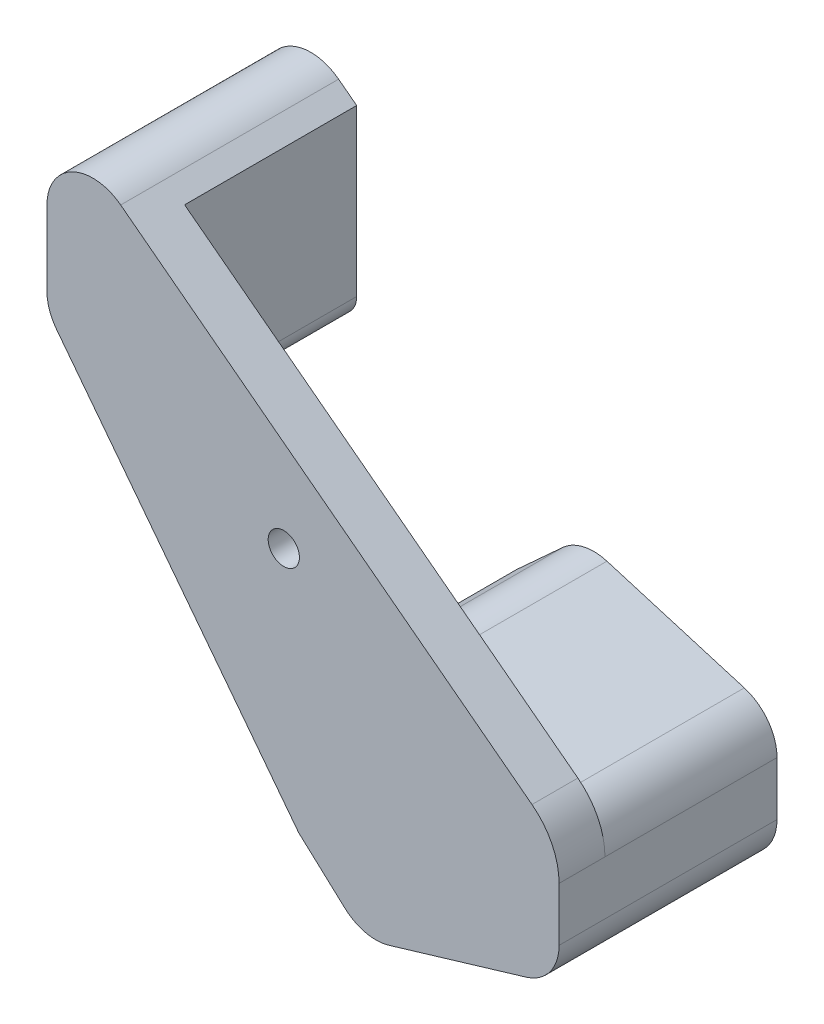
SolidWorks part; units mm, degrees
ref_plane "Front Plane" through (0, 0, 0) normal (0, 0, 1) x (1, 0, 0)
ref_plane "Top Plane" through (0, 0, 0) normal (0, 1, 0) x (1, 0, 0)
ref_plane "Right Plane" through (0, 0, 0) normal (1, 0, 0) x (0, 0, -1)
sketch "Sketch1" plane through (0, 0, 0) normal (0, 0, 1) x (1, 0, 0)
  line L0 (0, 0) -> (0, 12.7)
  line L1 (0, 12.7) -> (11.1125, 22.86)
  line L3 (11.1125, 22.86) -> (38.1, 14.7942)
  line L4 (38.1, 14.7942) -> (38.1, -19.05)
  line L5 (11.1125, 12.7) -> (11.1125, 0) construction
  line L6 (11.1125, 6.35) -> (30.1625, 6.35) construction
  line L7 (11.1125, -10.16) -> (38.1, -2.0942)
  line L8 (0, 0) -> (11.1125, -10.16)
  circle A0 centre (11.1125, 12.7) radius 2.032
  circle A1 centre (11.1125, 0) radius 2.032
  circle A2 centre (30.1625, 6.35) radius 2.032
  dimension "D3" = 4.064
  dimension "D1" = 73.36
  dimension "D2" = 38.1
  dimension "D4" = 11.1125
  dimension "D5" = 12.7
  dimension "D6" = 10.16
  dimension "D7" = 19.05
  dimension "D8" = 19.05
extrude "Boss-Extrude1" add sketch "Sketch1" along normal blind 23.8125 contours L0 L8 L7 L4 L3 L1 A2 A1 A0 region at (18.6064, 6.35, 0)
fillet "Fillet1" radius 6.35 6 edges at (38.1, 14.7942, 11.9062) (11.1125, 22.86, 11.9062) (0, 12.7, 11.9062) (38.1, -2.0942, 11.9062) (11.1125, -10.16, 11.9062) (0, 0, 11.9062)
sketch "Sketch3" plane through (0, 0, 23.8125) normal (0, 0, 1) x (1, 0, 0)
  line L0 (2.0652, -1.8882) -> (-32.7759, 43.4132)
  line L1 (-32.7759, 43.4132) -> (-32.7759, 68.8132)
  line L2 (-32.7759, 68.8132) -> (34.3497, 17.6393)
  line L6 (14.5601, -9.1296) -> (33.5684, -3.4485)
  line L7 (38.1, 2.6355) -> (38.1, 10.0645)
  line L8 (33.5684, 16.1485) -> (14.5601, 21.8296)
  line L9 (8.4569, 20.432) -> (2.0652, 14.5882)
  line L10 (0, 9.9017) -> (0, 2.7983)
  line L11 (2.0652, -1.8882) -> (8.4569, -7.732)
  line L12 (14.5601, -9.1296) -> (33.5684, -3.4485)
  line L13 (38.1, 2.6355) -> (38.1, 10.0645)
  line L17 (2.0652, -1.8882) -> (8.4569, -7.732)
  arc A0 (38.1, 10.0645) -> (34.3497, 17.6393) centre (28.575, 10.0645) ccw
  circle A1 centre (0, 31.1519) radius 2.159 construction
  circle A2 centre (0, 31.1519) radius 2.159
  arc A6 (33.5684, -3.4485) -> (38.1, 2.6355) centre (31.75, 2.6355) ccw
  arc A7 (38.1, 10.0645) -> (33.5684, 16.1485) centre (31.75, 10.0645) ccw
  arc A8 (14.5601, 21.8296) -> (8.4569, 20.432) centre (12.7417, 15.7455) ccw
  arc A9 (2.0652, 14.5882) -> (0, 9.9017) centre (6.35, 9.9017) ccw
  arc A10 (0, 2.7983) -> (2.0652, -1.8882) centre (6.35, 2.7983) ccw
  arc A11 (8.4569, -7.732) -> (14.5601, -9.1296) centre (12.7417, -3.0455) ccw
  arc A12 (33.5684, -3.4485) -> (38.1, 2.6355) centre (31.75, 2.6355) ccw
  arc A17 (8.4569, -7.732) -> (14.5601, -9.1296) centre (12.7417, -3.0455) ccw
  dimension "D2" = 57.15
  dimension "D3" = 9.525
  dimension "D4" = 170
  dimension "D5" = 25.4
  dimension "D1" = 0
extrude "Boss-Extrude2" add sketch "Sketch3" along normal blind 6.35
fillet "Fillet2" radius 6.35 2 edges at (-32.7759, 43.4132, 26.9875) (-32.7759, 68.8132, 26.9875)
sketch "Sketch4" plane through (0, 0, 23.8125) normal (0, 0, -1) x (-1, 0, 0)
  line L0 (32.7759, 55.9874) -> (32.7759, 45.5727) construction
  line L1 (32.7759, 55.9874) -> (32.7759, 45.5727)
  line L2 (22.5761, 61.0373) -> (20.0759, 59.1312)
  line L3 (-34.3497, 17.6393) -> (22.5761, 61.0373) construction
  line L4 (31.4594, 41.7014) -> (20.0759, 26.9003)
  line L5 (20.0759, 59.1312) -> (20.0759, 26.9003)
  arc A0 (31.4594, 41.7014) -> (32.7759, 45.5727) centre (26.4259, 45.5727) ccw construction
  arc A1 (32.7759, 55.9874) -> (22.5761, 61.0373) centre (26.4259, 55.9874) ccw construction
  arc A2 (31.4594, 41.7014) -> (32.7759, 45.5727) centre (26.4259, 45.5727) ccw
  arc A3 (32.7759, 55.9874) -> (22.5761, 61.0373) centre (26.4259, 55.9874) ccw
  circle A4 centre (26.4259, 55.9874) radius 2.032
  circle A5 centre (26.4259, 45.5727) radius 2.032
  dimension "D2" = 4.064
  dimension "D1" = 12.7
extrude "Boss-Extrude3" add sketch "Sketch4" along normal up to surface (23.8125 mm away)
ref_plane "Plane1" through (0, 0, -2.54) normal (0, 0, -1) x (-1, 0, 0)
fillet "Fillet3" radius 3.175 1 edges at (-20.0759, 26.9003, 11.9063)
mirror "Mirror2" [suppressed] about plane through (0, 0, -2.54) normal (0, 0, -1) of bodies 103
delete or keep bodies "Body-Delete/Keep 1" [suppressed] type delete bodies bodies 103
